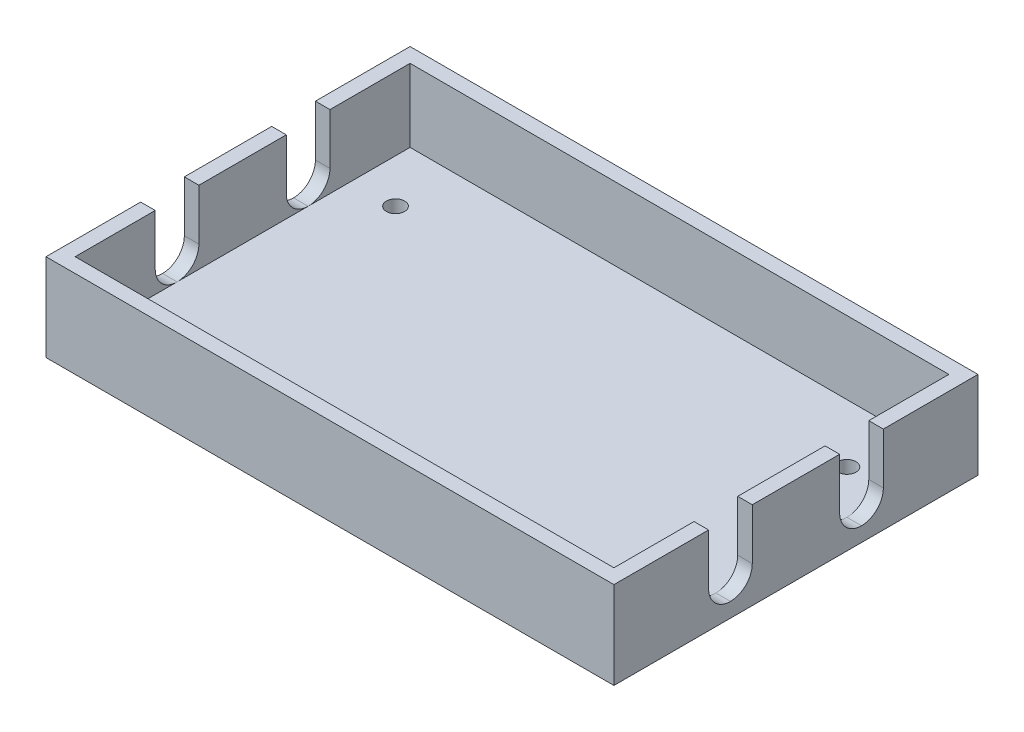
SolidWorks part; units mm, degrees
ref_plane "Płaszczyzna przednia" through (0, 0, 0) normal (0, 0, 1) x (1, 0, 0)
ref_plane "Płaszczyzna górna" through (0, 0, 0) normal (0, 1, 0) x (1, 0, 0)
ref_plane "Płaszczyzna prawa" through (0, 0, 0) normal (1, 0, 0) x (0, 0, -1)
sketch "Sketch2" plane through (0, 0, 0) normal (0, 0, 1) x (1, 0, 0)
  line L0 (0, 0) -> (17.5, 0) construction
  line L5 (0, 0) -> (-18.5, 0) construction
  line L7 (-18.5, 0) -> (-18.5, -2) construction
  line L8 (17.5, 0) -> (17.5, -1) construction
  line L9 (17.5, -1) -> (12.5, -1) construction
  line L10 (12.5, -1) -> (12.5, -8.5) construction
  line L11 (-18.5, -2) -> (-14.5, -2) construction
  line L12 (-14.5, -2) -> (-14.5, -8.5) construction
  line L13 (-14.5, -8.5) -> (12.5, -8.5) construction
  line L14 (-18.5, 0.5) -> (-18.5, -1) construction
  line L15 (-18.5, 0.5) -> (-18.5, -1)
  line L16 (-18.5, -1) -> (-14.5, -1)
  line L17 (-14.5, -1) -> (-14.5, -3.5)
  line L18 (-14.5, -3.5) -> (-21.5, -3.5)
  line L19 (-21.5, -3.5) -> (-21.5, -1)
  line L20 (-21.5, -1) -> (-21.5, 3)
  line L21 (-21.5, 3) -> (20.5, 3)
  line L22 (20.5, 3) -> (20.5, -3.5)
  line L23 (20.5, -3.5) -> (13.5, -3.5)
  line L24 (13.5, -3.5) -> (13.5, -1)
  line L25 (13.5, -1) -> (17.5, -1)
  line L26 (17.5, -1) -> (17.5, 0.5)
  line L27 (17.5, 0.5) -> (-18.5, 0.5)
  point P10 (-21.5, -1)
  point P11 (-21.5, -3.5)
  point P12 (-14.5, -3.5)
  point P13 (-21.5, -1)
  point P14 (-21.5, 3)
  point P16 (-14.5, -1)
  point P17 (-18.5, -1)
  point P18 (-18.5, 0.5)
  dimension "D3" = 4
  dimension "D4" = 4
  dimension "D5" = 42
  dimension "D6" = 0
  dimension "D7" = 3
  dimension "D8" = 3
  dimension "D9" = 7
  dimension "D10" = 7
  dimension "D11" = 2.5
  dimension "D12" = 6.5
  dimension "D13" = 6.5
  dimension "D14" = 1.5
  dimension "D15" = 36
  dimension "D16" = 2.5
  dimension "D17" = 1.5
  dimension "D22" = 0
  dimension "D23" = 0
extrude "Boss-Extrude1" add sketch "Sketch2" along normal blind 10
sketch "Sketch3" plane through (0, 3, 0) normal (0, 1, 0) x (1, 0, 0)
  line L0 (20.5, 0) -> (-21.5, 0) construction
  line L1 (-21.5, -10) -> (-21.5, 0) construction
  line L3 (38, -28) -> (-36, -28)
  line L4 (38, -28) -> (38, 18)
  line L5 (38, 18) -> (-36, 18)
  line L6 (-36, -28) -> (-36, 18)
  line L7 (38, -28) -> (-36, 18) construction
  line L8 (38, 18) -> (-36, -28) construction
  point P0 (1, -5)
  point P5 (1, -5)
  dimension "D1" = 5
  dimension "D2" = 22.5
  dimension "D3" = 46
  dimension "D4" = 74
extrude "Boss-Extrude2" add sketch "Sketch3" along normal blind 2
sketch "Sketch4" plane through (0, 5, 0) normal (0, 1, 0) x (1, 0, 0)
  line L0 (-36, 18) -> (38, -28) construction
  line L2 (38, 18) -> (-36, -28) construction
  line L3 (-30, -20) -> (32, -20) construction
  line L4 (-30, -20) -> (-30, 10) construction
  line L5 (-30, 10) -> (32, 10) construction
  line L6 (32, -20) -> (32, 10) construction
  line L7 (-30, -20) -> (32, 10) construction
  line L8 (-30, 10) -> (32, -20) construction
  circle A0 centre (-30, 10) radius 1.25
  circle A1 centre (-30, -20) radius 1.25
  circle A2 centre (32, 10) radius 1.25
  circle A3 centre (32, -20) radius 1.25
  point P8 (1, -5)
  dimension "D1" = 62
  dimension "D2" = 30
extrude "Cut-Extrude1" cut sketch "Sketch4" against normal blind 10
sketch "Sketch5" plane through (0, 5, 0) normal (0, 1, 0) x (1, 0, 0)
  line L0 (-36, 18) -> (38, -28) construction
  line L1 (38, -28) -> (38, 18) construction
  line L2 (38, -28) -> (38, 18) construction
  line L3 (38, 18) -> (-36, 18) construction
  line L4 (38, 18) -> (-36, -28) construction
  line L6 (-38, -30) -> (40, -30)
  line L7 (-38, -30) -> (-38, 20)
  line L8 (-38, 20) -> (40, 20)
  line L9 (40, -30) -> (40, 20)
  line L10 (-38, -30) -> (40, 20) construction
  line L11 (-38, 20) -> (40, -30) construction
  line L12 (-36, -28) -> (38, -28)
  line L13 (-36, -28) -> (-36, 18)
  line L14 (-36, 18) -> (38, 18)
  line L15 (38, -28) -> (38, 18)
  line L16 (-36, -28) -> (38, 18) construction
  line L17 (-36, 18) -> (38, -28) construction
  point P9 (1, -5)
  point P16 (1, -5)
  dimension "D1" = 78
  dimension "D2" = 50
extrude "Boss-Extrude3" add sketch "Sketch5" along normal blind 10 and the other way blind 2
sketch "Sketch9" plane through (0, 15, 0) normal (0, 1, 0) x (1, 0, 0)
  line L0 (-36, -5) -> (43.5415, -5) construction
  line L1 (-36, 18) -> (-36, -28) construction
  line L2 (43.5415, -5) -> (-54.723, -5) construction
  line L4 (-41.7383, 7) -> (44.5468, 7)
  line L5 (-41.7383, 7) -> (-41.7383, 1)
  line L6 (-41.7383, 1) -> (44.5468, 1)
  line L7 (44.5468, 7) -> (44.5468, 1)
  line L8 (-41.0682, -11) -> (42.8713, -11)
  line L9 (-41.0682, -11) -> (-41.0682, -17)
  line L10 (-41.0682, -17) -> (42.8713, -17)
  line L11 (42.8713, -11) -> (42.8713, -17)
  dimension "D1" = 6
  dimension "D2" = 6
  dimension "D3" = 6
  dimension "D4" = 6
extrude "Cut-Extrude2" cut sketch "Sketch9" against normal blind 10
fillet "Fillet1" radius 3 8 edges at (-37, 5, 17) (-37, 5, 11) (-37, 5, -7) (-37, 5, -1) (39, 5, 17) (39, 5, 11) (39, 5, -7) (39, 5, -1)
